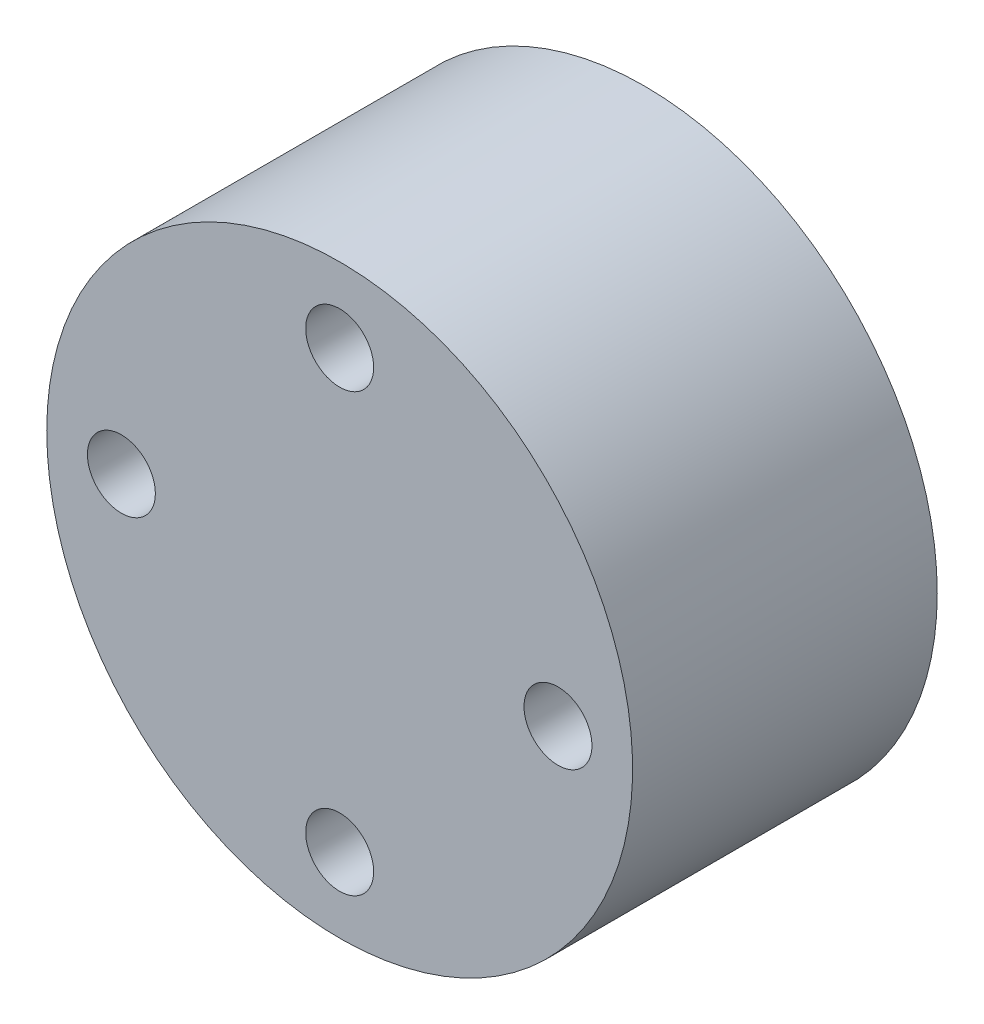
SolidWorks part; units mm, degrees
ref_plane "Front Plane" through (0, 0, 0) normal (0, 0, 1) x (1, 0, 0)
ref_plane "Top Plane" through (0, 0, 0) normal (0, 1, 0) x (1, 0, 0)
ref_plane "Right Plane" through (0, 0, 0) normal (1, 0, 0) x (0, 0, -1)
sketch "Sketch1" plane through (0, 0, 0) normal (0, 0, 1) x (1, 0, 0)
  circle A0 centre (0, 0) radius 12.5
  dimension "D1" = 25
extrude "Boss-Extrude1" add sketch "Sketch1" along normal mid plane 10
sketch "Sketch2" plane through (0, 0, 0) normal (1, 0, 0) x (0, 0, -1)
  line L0 (0, 0) -> (-9.3347, 0) construction
  line L1 (-8, 0) -> (-8, 12.5)
  line L3 (-5, 12.5) -> (-5, -12.5) construction
  line L4 (-5, 12.5) -> (-8, 12.5)
  line L5 (-5, 12.5) -> (-5, 0)
  line L6 (-5, 0) -> (-8, 0)
  point P8 (0, 0)
  point P10 (0, 0)
  dimension "D1" = 12.5
  dimension "D2" = 3
  dimension "D3" = 0
revolve "Revolve1" add sketch "Sketch2" angle 360 about L0
sketch "Sketch5" plane through (0, 0, 8) normal (0, 0, 1) x (1, 0, 0)
  circle A0 centre (0, 9.315) radius 1.45
  circle A1 centre (0, 9.315) radius 1.45 construction
  circle A2 centre (9.315, 0) radius 1.45
  circle A3 centre (0, -9.315) radius 1.45
  circle A4 centre (-9.315, 0) radius 1.45
  point P14 (0, 0)
  dimension "D1" = 0
  dimension "D2" = 4
extrude "Cut-Extrude1" cut sketch "Sketch5" against normal blind 5
sketch "Sketch6" plane through (0, 0, -5) normal (0, 0, -1) x (-1, 0, 0)
  circle A7 centre (0, 8) radius 1.45
  circle A8 centre (8, 0) radius 1.45
  circle A9 centre (0, -8) radius 1.45
  circle A10 centre (-8, 0) radius 1.45
  point P12 (0, 0)
  point P14 (0, 0)
  dimension "D1" = 2.9
  dimension "D2" = 4
  dimension "D3" = 16
extrude "Cut-Extrude2" cut sketch "Sketch6" against normal blind 5
